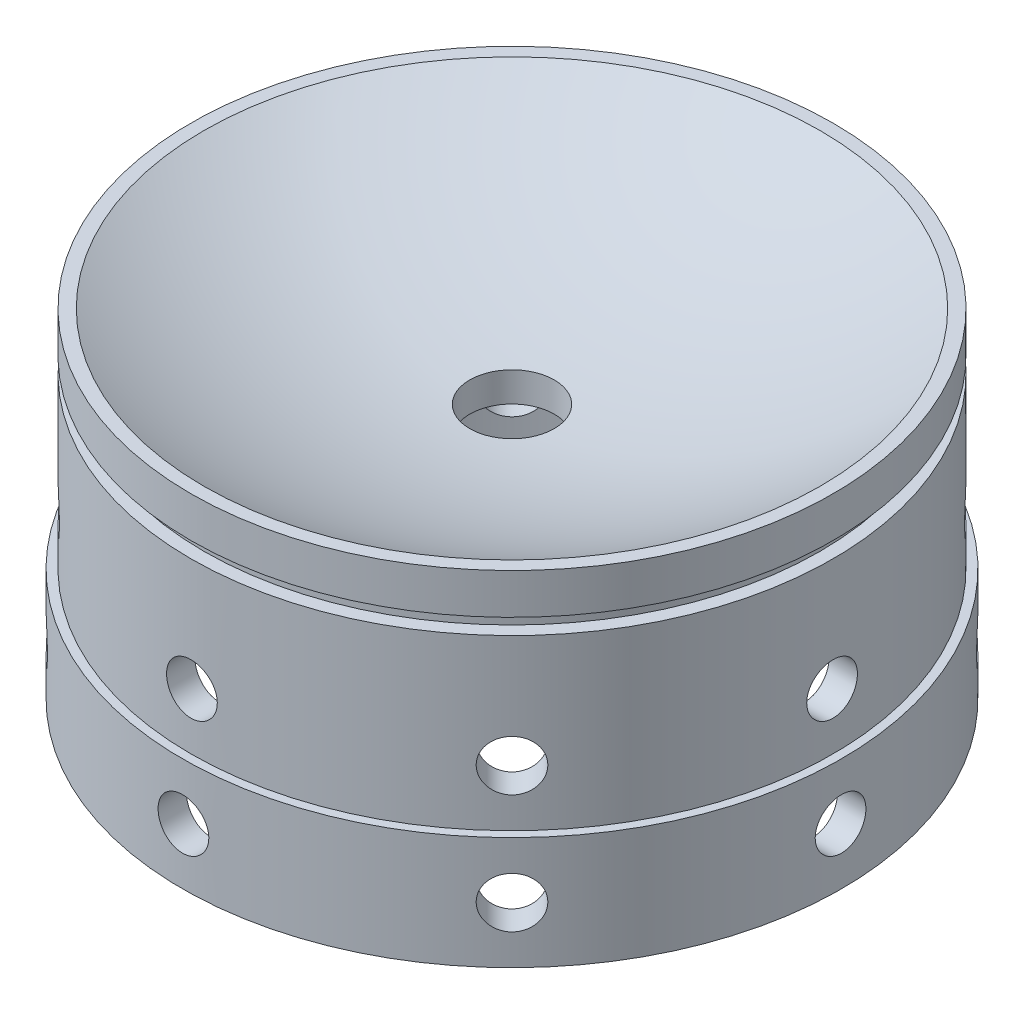
SolidWorks part; units mm, degrees
ref_plane "Front Plane" through (0, 0, 0) normal (0, 0, 1) x (1, 0, 0)
ref_plane "Top Plane" through (0, 0, 0) normal (0, 1, 0) x (1, 0, 0)
ref_plane "Right Plane" through (0, 0, 0) normal (1, 0, 0) x (0, 0, -1)
sketch "Sketch1" plane through (0, 0, 0) normal (0, 0, 1) x (1, 0, 0)
  line L0 (0, 0) -> (0, 6.35)
  line L1 (0, 0) -> (72.39, 0)
  line L2 (72.39, 0) -> (72.39, 12.7)
  line L3 (72.39, 12.7) -> (69.469, 12.7)
  line L4 (69.469, 12.7) -> (69.469, 16.256)
  line L5 (69.469, 16.256) -> (72.39, 16.256)
  line L6 (72.39, 16.256) -> (72.39, 25.4)
  line L7 (72.39, 25.4) -> (69.469, 25.4)
  line L8 (69.469, 25.4) -> (69.469, 6.35) construction
  line L9 (69.469, 6.35) -> (0, 6.35) construction
  line L10 (72.39, 0) -> (72.39, -25.4)
  line L11 (72.39, -25.4) -> (66.04, -25.4)
  line L12 (66.04, -25.4) -> (66.04, 0)
  line L13 (74.93, 68.1653) -> (74.93, 53.6699) construction
  line L14 (67.945, -50.8) -> (67.945, -25.4)
  line L15 (67.945, -50.8) -> (74.295, -50.8)
  line L16 (9.525, 6.6835) -> (9.525, 0)
  line L17 (73.025, 45.3691) -> (73.025, 21.7883) construction
  line L18 (74.295, -50.8) -> (74.295, -25.4)
  line L19 (74.295, -25.4) -> (72.39, -25.4)
  arc A0 (69.469, 25.4) -> (0, 6.35) centre (0, 142.5401) cw
  dimension "D1" = 72.39
  dimension "D5" = 25.4
  dimension "D9" = 6.35
  dimension "D12" = 9.525
  dimension "D3" = 12.7
  dimension "D4" = 3.556
  dimension "D2" = 73.025
  dimension "D13" = 3.556
  dimension "D6" = 6.35
  dimension "D7" = 25.4
  dimension "D8" = 74.93
  dimension "D10" = 25.4
  dimension "D11" = 74.295
revolve "Revolve1" add sketch "Sketch1" angle 360 about L0 region at (48.1528, 8.1766, 0) region at (69.215, -12.7, 0) region at (71.12, -38.1, 0)
hole_wizard "1/2 (0.45) Diameter Hole1" positions "3DSketch5" profile "Sketch8" hole size "1/2" standard "ANSI Inch"
sketch3d "3DSketch5"
  line L0 (0, -25.4, 0) -> (0, 0, 0) construction
  line L2 (0, -12.7, 0) -> (72.39, -12.7, 0)
  circle A8 centre (0, -25.4, 0) radius 72.39 construction
  circle A9 centre (0, -25.4, 0) radius 72.39
  point P0 (72.39, -12.7, 0)
  point P41 (0, -97.79, 0)
  point P43 (0, -97.79, 0)
  point P53 (72.39, -12.7, 0)
  point P57 (0, 0, 0)
  point P58 (0, 0, 0)
  point P59 (0, 0, 0)
  point P60 (57.7746, -12.7, 0)
  point P61 (62.5647, -8.5545, 36.4139)
sketch "Sketch8" plane through (72.39, -12.7, 0) normal (0, 1, 0) x (0, 0, -1)
  line L0 (0, 0) -> (0, 75.8229)
  line L1 (0, 75.8229) -> (5.715, 72.389)
  line L2 (5.715, 72.389) -> (5.715, 0)
  line L5 (5.715, 0) -> (0, 0)
  line L10 (0, 75.8229) -> (-5.715, 72.389) construction
  line L11 (0, -6.35) -> (0, 107.95) construction
  dimension "Hole Dia." = 11.43
  dimension "Hole Depth" = 72.389
  dimension "Drill Angle" = 118
hole_wizard "1/2 (0.45) Diameter Hole2" positions "3DSketch6" profile "Sketch9" hole size "1/2" standard "ANSI Inch"
sketch3d "3DSketch6"
  line L0 (0, -25.4, 0) -> (0, -50.8, 0)
  line L2 (0, -38.1, 0) -> (74.295, -38.1, 0)
  circle A0 centre (0, -50.8, 0) radius 74.295 construction
  circle A1 centre (0, -25.4, 0) radius 74.295 construction
  circle A2 centre (0, -50.8, 0) radius 74.295
  circle A3 centre (0, -25.4, 0) radius 74.295
  point P0 (74.295, -38.1, 0)
  point P5 (0, -125.095, 0)
  point P8 (0, -99.695, 0)
  point P10 (0, -125.095, 0)
  point P12 (0, -99.695, 0)
  point P19 (45.1853, -17.5198, 59.7729)
sketch "Sketch9" plane through (74.295, -38.1, 0) normal (0, 1, 0) x (0, 0, -1)
  line L0 (0, 0) -> (0, 77.7279)
  line L1 (0, 77.7279) -> (5.715, 74.294)
  line L2 (5.715, 74.294) -> (5.715, 0)
  line L5 (5.715, 0) -> (0, 0)
  line L10 (0, 77.7279) -> (-5.715, 74.294) construction
  line L11 (0, -6.35) -> (0, 107.95) construction
  dimension "Hole Dia." = 11.43
  dimension "Hole Depth" = 74.294
  dimension "Drill Angle" = 118
ref_axis "CenterAxis" through (0, 6.6835, 0) along (0, -1, 0)
chamfer "Chamfer1" distance 2.54 angle 45 1 edges at (0, -25.4, -67.945)
pattern_circular "CirPattern1" count 8 over 360 about axis through (0, -25.4, 0) along (0, -1, 0) of "1/2 (0.45) Diameter Hole1", "1/2 (0.45) Diameter Hole2"
equation "\"D1@Sketch1\"=(5.75/2)-(0.025in)"
equation "\"D12@Sketch1\"=0.75/2"
equation "\"D2@Sketch1\"=5.75/2"
equation "\"D8@Sketch1\"=5.9/2"
equation "\"D11@Sketch1\"=5.9/2 - (0.025in)"
